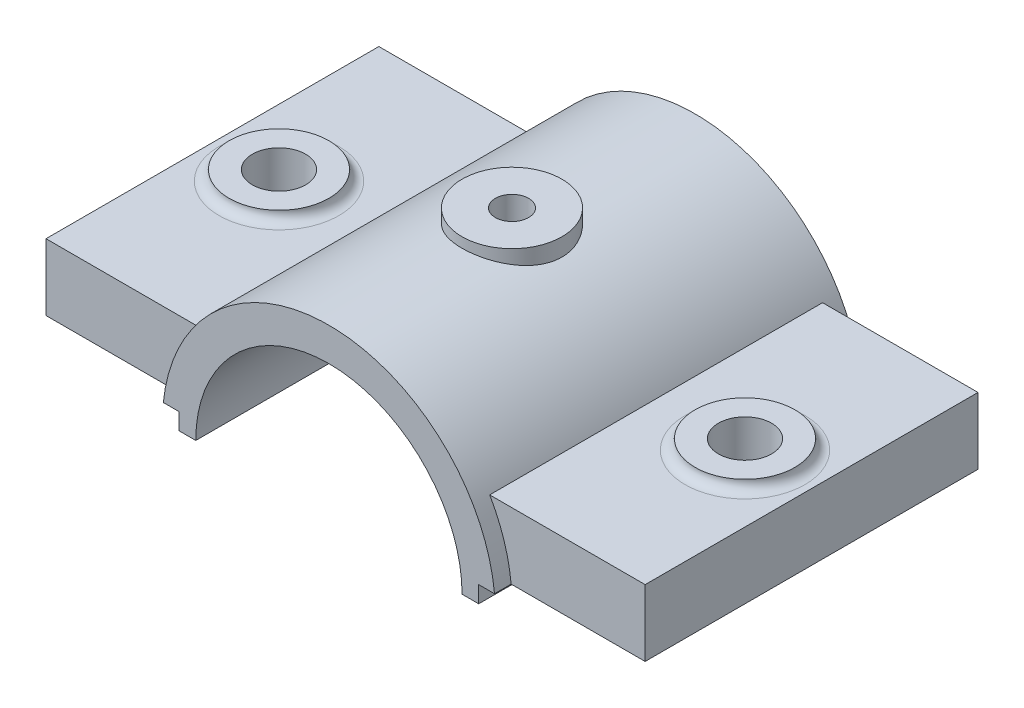
SolidWorks part; units mm, degrees
ref_plane "Front Plane" through (0, 0, 0) normal (0, 0, 1) x (1, 0, 0)
ref_plane "Top Plane" through (0, 0, 0) normal (0, 1, 0) x (1, 0, 0)
ref_plane "Right Plane" through (0, 0, 0) normal (1, 0, 0) x (0, 0, -1)
sketch "Sketch1" plane through (0, 0, 0) normal (0, 0, 1) x (1, 0, 0)
  line L0 (-50, 0) -> (50, 0)
  arc A0 (50, 0) -> (-50, 0) centre (0, 0) ccw
  dimension "D1" = 50
extrude "Boss-Extrude1" add sketch "Sketch1" along normal mid plane 110
sketch "Sketch2" plane through (0, 0, 0) normal (0, 0, 1) x (1, 0, 0)
  line L0 (-50, 0) -> (50, 0) construction
  line L1 (-90, 25) -> (90, 25)
  line L2 (-90, 25) -> (-90, 5)
  line L3 (-90, 5) -> (90, 5)
  line L4 (90, 25) -> (90, 5)
  line L5 (0, 0) -> (0, 69.1693) construction
  dimension "D1" = 5
  dimension "D2" = 20
  dimension "D3" = 180
extrude "Boss-Extrude2" add sketch "Sketch2" along normal mid plane 100
sketch "Sketch3" plane through (0, 0, 55) normal (0, 0, 1) x (1, 0, 0)
  line L0 (-50, 0) -> (50, 0) construction
  line L1 (45, 5) -> (50, 5)
  line L2 (45, 5) -> (45, 0)
  line L3 (45, 0) -> (50, 0)
  line L4 (50, 5) -> (50, 0)
  point P7 (50, 0)
  dimension "D1" = 5
  dimension "D2" = 5
extrude "Cut-Extrude1" cut sketch "Sketch3" against normal through all both and the other way through all
mirror "Mirror1" about plane through (0, 0, 0) normal (1, 0, 0) of "Cut-Extrude1"
sketch "Sketch4" plane through (0, 0, 55) normal (0, 0, 1) x (1, 0, 0)
  line L0 (-45, 0) -> (45, 0) construction
  line L1 (40, 0) -> (-40, 0)
  arc A0 (-40, 0) -> (40, 0) centre (0, 0) cw
  dimension "D1" = 40
extrude "Cut-Extrude2" cut sketch "Sketch4" against normal through all and the other way through all
sketch "Sketch5" plane through (0, 25, 0) normal (0, 1, 0) x (1, 0, 0)
  line L0 (-90, -50) -> (-90, 50) construction
  circle A0 centre (-70, 0) radius 15
  dimension "D1" = 30
  dimension "D2" = 20
  dimension "D3" = 70
extrude "Boss-Extrude3" add sketch "Sketch5" along normal blind 3
mirror "Mirror2" about plane through (0, 0, 0) normal (1, 0, 0) of "Boss-Extrude3"
ref_plane "Plane1" through (0, 53, 0) normal (0, 1, 0) x (1, 0, 0)
sketch "Sketch6" plane through (0, 53, 0) normal (0, 1, 0) x (1, 0, 0)
  circle A0 centre (0, 0) radius 15
  dimension "D1" = 30
extrude "Boss-Extrude4" add sketch "Sketch6" against normal up to next
hole_wizard "Hole1" positions "Sketch7" profile "Sketch8" legacy end condition through all
sketch "Sketch7" plane through (0, 53, 0) normal (0, 1, 0) x (1, 0, 0)
  point P0 (0, 0)
sketch "Sketch8" plane through (0, 53, 0) normal (1, 0, 0) x (0, 0, 1)
  line L0 (0, 0) -> (0, 53)
  line L1 (0, 53) -> (5, 53)
  line L2 (5, 53) -> (5, 0)
  line L3 (5, 0) -> (0, 0)
  line L4 (0, 110) -> (0, -10) construction
  dimension "Diameter" = 10
  dimension "Depth" = 53
hole_wizard "Hole2" positions "Sketch9" profile "Sketch10" legacy end condition through all
sketch "Sketch9" plane through (0, 28, 0) normal (0, 1, 0) x (1, 0, 0)
  point P0 (-70, 0)
  point P3 (70, 0)
  point P7 (0, 0)
sketch "Sketch10" plane through (-70, 28, 0) normal (1, 0, 0) x (0, 0, 1)
  line L0 (0, 0) -> (0, 28)
  line L1 (0, 28) -> (8, 28)
  line L2 (8, 28) -> (8, 0)
  line L3 (8, 0) -> (0, 0)
  line L4 (0, 110) -> (0, -10) construction
  dimension "Diameter" = 16
  dimension "Depth" = 28
fillet "Fillet1" radius 3 2 edges at (-70, 25, -15) (70, 25, 15)
sketch "Sketch11" plane through (0, 0, 0) normal (0, 1, 0) x (1, 0, 0)
  circle A0 centre (0, 0) radius 8
  dimension "D1" = 16
extrude "Cut-Extrude3" cut sketch "Sketch11" along normal blind 42
